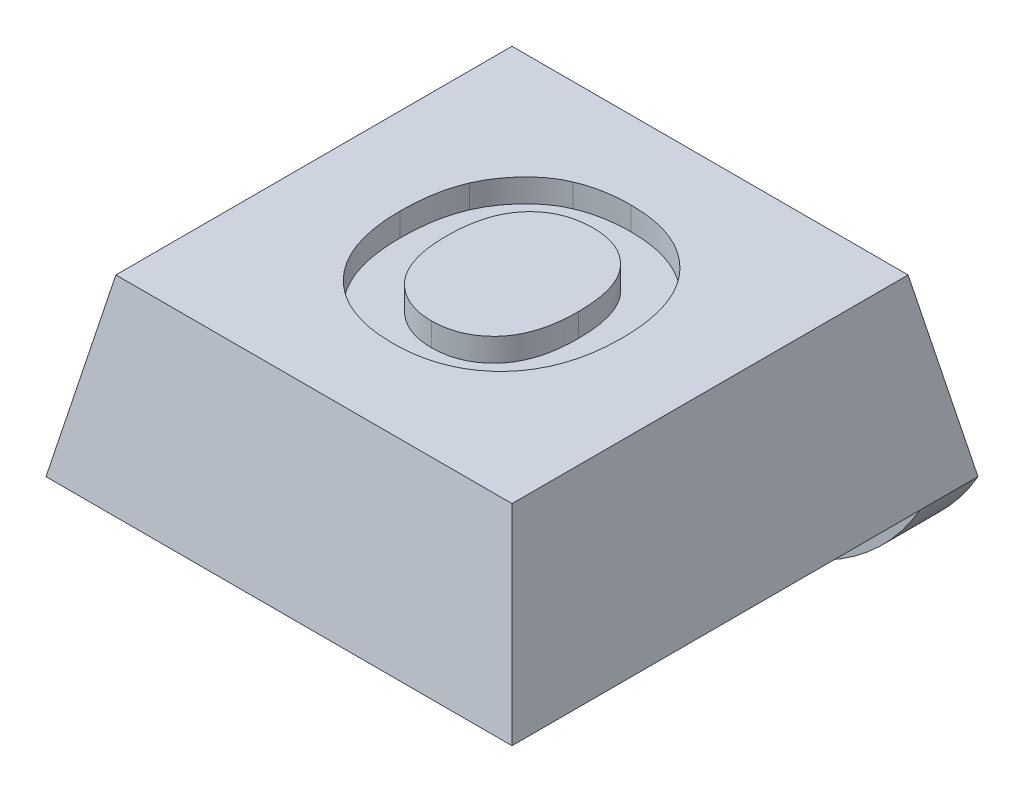
SolidWorks part; units mm, degrees
ref_plane "Front Plane" through (0, 0, 0) normal (0, 0, 1) x (1, 0, 0)
ref_plane "Top Plane" through (0, 0, 0) normal (0, 1, 0) x (1, 0, 0)
ref_plane "Right Plane" through (0, 0, 0) normal (1, 0, 0) x (0, 0, -1)
sketch "Sketch1" plane through (0, 0, 0) normal (0, 1, 0) x (1, 0, 0)
  line L1 (0, 0) -> (8, 0)
  line L2 (0, 0) -> (0, 8)
  line L3 (0, 8) -> (8, 8)
  line L4 (8, 0) -> (8, 8)
  dimension "D1" = 8
  dimension "D2" = 8
extrude "Boss-Extrude1" add sketch "Sketch1" along normal blind 3
sketch "Sketch2" plane through (0, 0, 0) normal (0, 0, 1) x (1, 0, 0)
  line L0 (0, 0) -> (0.6, 3)
  line L1 (0, 3) -> (8, 3) construction
  line L2 (0.6, 3) -> (0, 3)
  line L3 (0, 3) -> (0, 0)
  line L4 (8, 0) -> (7.4, 3)
  line L5 (7.4, 3) -> (8, 3)
  line L6 (8, 3) -> (8, 0)
  dimension "D1" = 0.6
  dimension "D2" = 0.6
extrude "Cut-Extrude1" cut sketch "Sketch2" against normal through all both and the other way through all
sketch "Sketch3" plane through (0, 0, 0) normal (1, 0, 0) x (0, 0, -1)
  line L0 (0, 0) -> (0.6, 3)
  line L1 (8, 3) -> (0, 3) construction
  line L2 (0.6, 3) -> (0, 3)
  line L3 (0, 3) -> (0, 0)
  line L4 (8, 3) -> (7.4, 3)
  line L5 (7.4, 3) -> (8, 0)
  line L6 (8, 3) -> (8, 0)
  dimension "D1" = 0.6
  dimension "D2" = 0.6
extrude "Cut-Extrude2" cut sketch "Sketch3" along normal blind 11
sketch "Sketch4" plane through (0, 0, 0) normal (0, -1, 0) x (1, 0, 0)
  line L0 (8, 0) -> (8, -8) construction
  line L3 (0, 0) -> (8, 0) construction
  circle A0 centre (4, -3.75) radius 1.8
  dimension "D1" = 3.6
  dimension "D2" = 4
  dimension "D3" = 3.75
extrude "Cut-Extrude3" cut sketch "Sketch4" against normal blind 0.8
sketch "Sketch5" plane through (0, 0, 0) normal (0, -1, 0) x (1, 0, 0)
  line L0 (8, 0) -> (8, -8) construction
  line L1 (0, -8) -> (8, -8)
  line L2 (0, -8) -> (0, -7)
  line L3 (0, -7) -> (8, -7)
  line L4 (8, -8) -> (8, -7)
  dimension "D1" = 1
extrude "Boss-Extrude2" add sketch "Sketch5" along normal blind 2
fillet "Fillet1" radius 4 2 edges at (8, -2, -7.5) (0, -2, -7.5)
sketch "Sketch6" plane through (0, 3, 0) normal (0, 1, 0) x (1, 0, 0)
  text T0 "O" font "Arial" height 4
extrude "Cut-Extrude4" cut sketch "Sketch6" against normal blind 0.4
